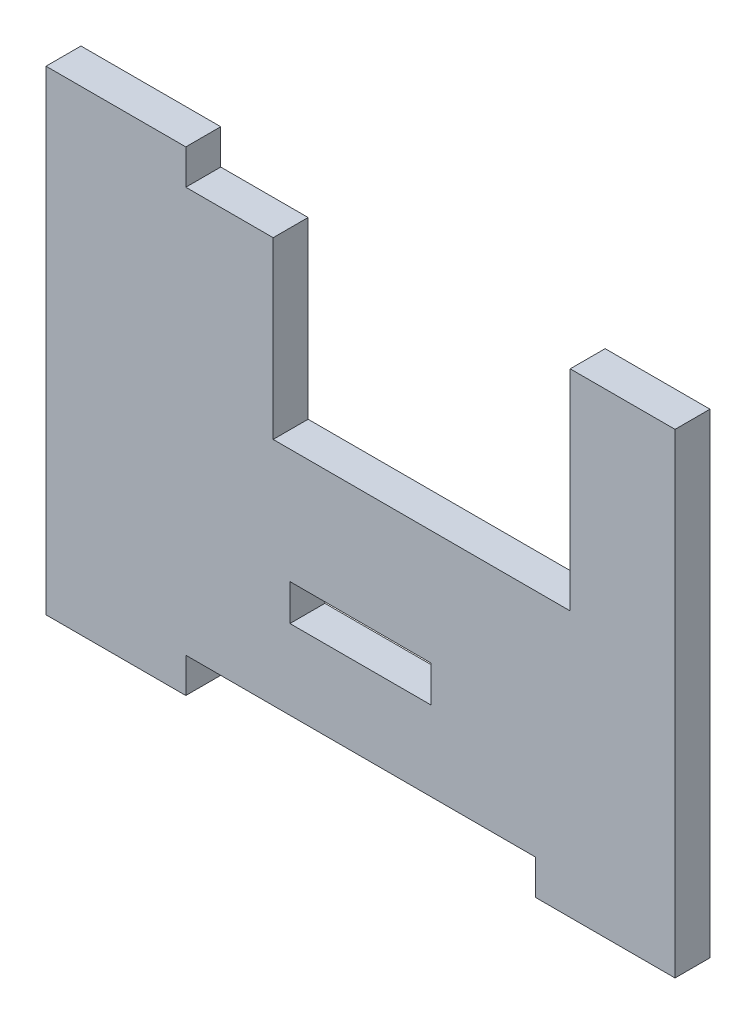
SolidWorks part; units mm, degrees
ref_plane "Front Plane" through (0, 0, 0) normal (0, 0, 1) x (1, 0, 0)
ref_plane "Top Plane" through (0, 0, 0) normal (0, 1, 0) x (1, 0, 0)
ref_plane "Right Plane" through (0, 0, 0) normal (1, 0, 0) x (0, 0, -1)
sketch "Sketch2" plane through (0, 0, 0) normal (0, 0, -1) x (1, 0, 0)
  line L0 (-139.7, 73.64) -> (-139.7, 0) construction
  line L1 (0, 0) -> (-279.4, 0) construction
  line L2 (0, 0) -> (0, 73.64) construction
  line L3 (0, 73.64) -> (-82.55, 73.64)
  line L4 (-279.4, 0) -> (-279.4, 73.64) construction
  line L5 (-82.55, 73.64) -> (-82.55, 0)
  line L6 (-196.85, 73.64) -> (-196.85, 0)
  line L7 (-101.6, 0) -> (-101.6, 31.75)
  line L8 (-101.6, 31.75) -> (-155.575, 31.75)
  line L9 (-155.575, 31.75) -> (-155.575, 0)
  line L10 (-171.45, 73.64) -> (-171.45, 79.99)
  line L12 (-82.55, 73.64) -> (-82.55, 79.99)
  line L13 (-82.55, 79.99) -> (-107.95, 79.99)
  line L14 (-107.95, 73.64) -> (-107.95, 79.99)
  line L15 (-196.85, 79.99) -> (-171.45, 79.99)
  line L16 (-196.85, 73.64) -> (-196.85, 79.99)
  line L18 (-107.95, 73.64) -> (-171.45, 73.64)
  line L19 (-196.85, 73.64) -> (-279.4, 73.64) construction
  line L20 (-155.575, 0) -> (-171.45, 0)
  line L21 (-82.55, 0) -> (-101.6, 0) construction
  line L22 (-82.55, 0) -> (-82.55, -6.35)
  line L23 (-82.55, -6.35) -> (-101.6, -6.35)
  line L24 (-101.6, 0) -> (-101.6, -6.35)
  line L25 (-196.85, 0) -> (-171.45, 0) construction
  line L26 (-196.85, 0) -> (-196.85, -6.35)
  line L27 (-196.85, -6.35) -> (-171.45, -6.35)
  line L28 (-171.45, 0) -> (-171.45, -6.35)
  line L37 (-126.873, 59.197) -> (-152.527, 59.197)
  line L38 (-152.527, 59.197) -> (-152.527, 52.593)
  line L39 (-152.527, 52.593) -> (-126.873, 52.593)
  line L40 (-126.873, 52.593) -> (-126.873, 59.197)
  line L41 (-126.873, 59.197) -> (-152.527, 59.197)
  line L42 (-152.527, 59.197) -> (-152.527, 52.593)
  line L43 (-152.527, 52.593) -> (-126.873, 52.593)
  line L44 (-126.873, 52.593) -> (-126.873, 59.197)
  dimension "D1" = 279.4
  dimension "D2" = 73.64
  dimension "D3" = 114.3
  dimension "D4" = 19.05
  dimension "D5" = 31.75
  dimension "D6" = 53.975
  dimension "D7" = 25.4
  dimension "D8" = 6.35
  dimension "D9" = 6.35
  dimension "D10" = 6.35
  dimension "D11" = 25.4
  dimension "D12" = 0.127
extrude "Boss-Extrude1" add sketch "Sketch2" along normal blind 6.35 contours L20 L28 L27 L26 L6 L16 L15 L10 L18 L14 L13 L12 L5 L22 L23 L24 L7 L8 L9 region at (-142.5649, -41.6212, 0)
